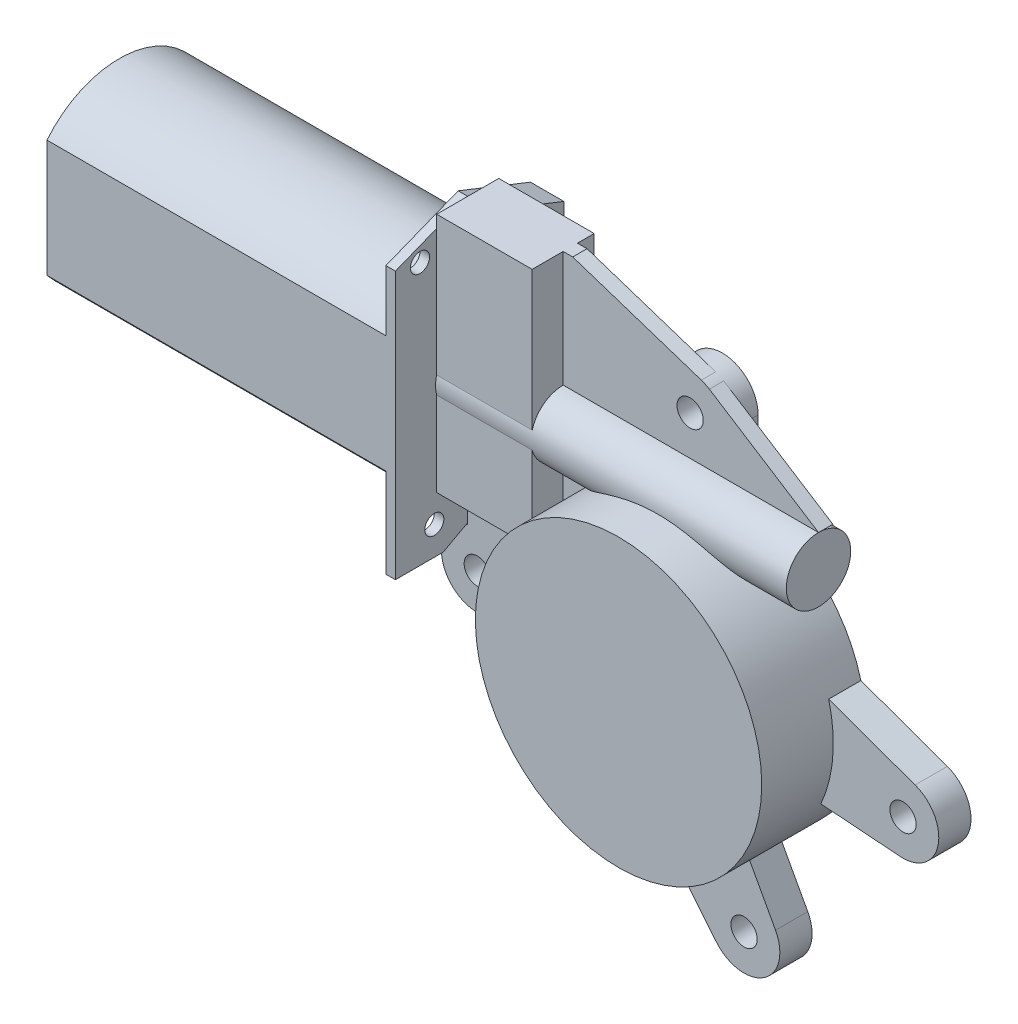
SolidWorks part; units mm, degrees
ref_plane "正面" through (0, 0, 0) normal (0, 0, 1) x (1, 0, 0)
ref_plane "平面" through (0, 0, 0) normal (0, 1, 0) x (1, 0, 0)
ref_plane "右側面" through (0, 0, 0) normal (1, 0, 0) x (0, 0, -1)
sketch "ｽｹｯﾁ2" plane through (0, 0, 0) normal (1, 0, 0) x (0, 0, -1)
  line L0 (0, 0) -> (0, 50000) construction
  line L1 (15.15, 12.2771) -> (15.15, -12.2771)
  line L2 (-15.15, 12.2771) -> (-15.15, -12.2771)
  arc A0 (-15.15, -12.2771) -> (15.15, -12.2771) centre (0, 0) ccw
  arc A2 (15.15, 12.2771) -> (-15.15, 12.2771) centre (0, 0) ccw
  dimension "D1" = 39
  dimension "D2" = 30.3
extrude "ﾎﾞｽ - 押し出し1" add sketch "ｽｹｯﾁ2" against normal blind 71
sketch "ｽｹｯﾁ3" plane through (-71, 0, 0) normal (-1, 0, 0) x (0, 0, 1)
  circle A0 centre (0, 0) radius 7
  dimension "D1" = 14
extrude "ﾎﾞｽ - 押し出し2" add sketch "ｽｹｯﾁ3" along normal blind 0.8
sketch "ｽｹｯﾁ4" plane through (-71.8, 0, 0) normal (-1, 0, 0) x (0, 0, 1)
  circle A0 centre (0, 0) radius 2.25
  dimension "D1" = 4.5
extrude "ﾎﾞｽ - 押し出し3" add sketch "ｽｹｯﾁ4" along normal blind 0.2
sketch "ｽｹｯﾁ5" plane through (0, 0, 0) normal (1, 0, 0) x (0, 0, -1)
  line L0 (0, 0) -> (0, 50000) construction
  line L1 (0, 0) -> (-50000, 0) construction
  line L2 (-15.15, 25) -> (-15.15, -20)
  line L3 (-15.15, -20) -> (5.15, -31)
  line L4 (5.15, -31) -> (15.15, -31)
  line L5 (15.15, -31) -> (15.15, 25)
  line L6 (15.15, 25) -> (0, 31)
  line L7 (0, 31) -> (-15.15, 25)
  line L8 (15.15, -12.2771) -> (15.15, 12.2771) construction
  line L9 (-15.15, 12.2771) -> (-15.15, -12.2771) construction
  circle A0 centre (0, 0) radius 26 construction
  circle A1 centre (0, 26) radius 2.5
  circle A2 centre (-10, 24) radius 2
  circle A3 centre (10, 24) radius 2
  circle A4 centre (7, -25.04) radius 2
  dimension "D6" = 52
  dimension "D8" = 5
  dimension "D9" = 4
  dimension "D10" = 7
  dimension "D11" = 4
  dimension "D2" = 31
  dimension "D3" = 25
  dimension "D4" = 62
  dimension "D5" = 20
  dimension "D7" = 10
  dimension "D12" = 10
extrude "ﾎﾞｽ - 押し出し4" add sketch "ｽｹｯﾁ5" along normal blind 2
sketch "ｽｹｯﾁ7" plane through (2, 0, 0) normal (1, 0, 0) x (0, 0, -1)
  circle A0 centre (0, 0) radius 6.75
  dimension "D1" = 13.5
extrude "ﾎﾞｽ - 押し出し7" add sketch "ｽｹｯﾁ7" along normal blind 73.5
sketch "ｽｹｯﾁ6" plane through (0, 0, 0) normal (0, 0, 1) x (1, 0, 0)
  line L0 (0, 0) -> (-50000, 0) construction
  line L1 (29.7505, -30) -> (-49970.2495, -30) construction
  line L2 (48.6, -30) -> (48.6, 49970) construction
  line L3 (2, 25) -> (2, -20) construction
  circle A0 centre (48.6, -30) radius 30
  dimension "D1" = 30
  dimension "D2" = 46.6
extrude "ﾎﾞｽ - 押し出し8" add sketch "ｽｹｯﾁ6" against normal blind 15
sketch "ｽｹｯﾁ8" plane through (0, 0, 0) normal (0, 0, 1) x (1, 0, 0)
  line L0 (48.6, -30) -> (48.6, 49970) construction
  line L1 (48.6, -30) -> (-49951.4, -30) construction
  line L2 (48.6, -36) -> (-49951.4, -36) construction
  line L3 (59.9, -30) -> (59.9, 49970) construction
  line L4 (54.1031, -78.2588) -> (37.3, -57.7905)
  line L5 (66.4901, -69.9194) -> (59.9, -57.7905)
  line L6 (92.6469, -43.4796) -> (75.9861, -42.2476)
  line L7 (95.741, -28.9436) -> (77.6268, -22.4207)
  line L8 (41.1, 15) -> (41.1, -0.9526)
  line L9 (56.1, 15) -> (56.1, -0.9526)
  line L10 (0.5475, -29.3419) -> (20.7407, -18.8709)
  line L11 (5.7319, -43.2973) -> (20.2627, -39.8487)
  arc A0 (41.1, -0.9526) -> (20.7407, -18.8709) centre (48.6, -30) ccw
  circle A1 centre (48.6, 15) radius 2.75
  circle A2 centre (4, -36) radius 2.75
  circle A3 centre (93.2, -36) radius 2.75
  circle A4 centre (59.9, -73.5) radius 2.75
  arc A5 (0.5475, -29.3419) -> (5.7319, -43.2973) centre (4, -36) ccw
  arc A6 (56.1, 15) -> (41.1, 15) centre (48.6, 15) ccw
  arc A7 (92.6469, -43.4796) -> (95.741, -28.9436) centre (93.2, -36) ccw
  arc A8 (54.1031, -78.2588) -> (66.4901, -69.9194) centre (59.9, -73.5) ccw
  arc A9 (29.6412, -6.75) -> (67.5588, -6.75) centre (48.6, -30) ccw construction
  arc A10 (59.9, -57.7905) -> (75.9861, -42.2476) centre (48.6, -30) ccw
  arc A11 (20.2627, -39.8487) -> (37.3, -57.7905) centre (48.6, -30) ccw
  arc A12 (77.6268, -22.4207) -> (56.1, -0.9526) centre (48.6, -30) ccw
  dimension "D3" = 60
  dimension "D4" = 43.5
  dimension "D5" = 44.6
  dimension "D6" = 44.6
  dimension "D8" = 5.5
  dimension "D9" = 15
  dimension "D1" = 11.3
  dimension "D2" = 6
  dimension "D7" = 45
extrude "ﾎﾞｽ - 押し出し9" add sketch "ｽｹｯﾁ8" along normal blind 6.75
sketch "ｽｹｯﾁ9" plane through (0, 0, 0) normal (0, 0, 1) x (1, 0, 0)
  line L0 (75.5, 6.75) -> (52.6308, 21.3247)
  line L1 (50.9466, 22.1235) -> (24, 31)
  line L2 (24, 31) -> (2, 31)
  line L3 (2, 31) -> (2, -28.5887)
  line L4 (20.7407, -18.8709) -> (0.5475, -29.3419) construction
  line L5 (2, -20) -> (2, -31) construction
  line L6 (2, -28.5887) -> (75.5, 6.75)
  arc A0 (56.1, 15) -> (41.1, 15) centre (48.6, 15) ccw construction
  arc A1 (50.9466, 22.1235) -> (52.6308, 21.3247) centre (48.6, 15) cw
  circle A2 centre (48.6, 15) radius 2.75
  dimension "D2" = 5.5
  dimension "D1" = 22
extrude "ﾎﾞｽ - 押し出し10" add sketch "ｽｹｯﾁ9" along normal blind 3 contours A1 L1 L2 L3 L6 L0 region at (28.0225, 5.7047, 0)
sketch "ｽｹｯﾁ10" plane through (0, 0, 0) normal (0, 0, 1) x (1, 0, 0)
  line L0 (2, 31) -> (22, 31)
  line L1 (24, 31) -> (2, 31) construction
  line L2 (22, 31) -> (22, -19.5)
  line L3 (22, -19.5) -> (2, -19.5)
  line L4 (2, 25) -> (2, -20) construction
  line L5 (2, -6.0467) -> (2, -26.5837) construction
  line L6 (-71, -19.5) -> (0, -19.5) construction
  line L7 (2, 31) -> (2, -19.5)
  dimension "D1" = 20
extrude "ﾎﾞｽ - 押し出し11" add sketch "ｽｹｯﾁ10" against normal blind 6.5 and the other way blind 6.5
sketch "ｽｹｯﾁ12" plane through (2, 0, 0) normal (1, 0, 0) x (0, 0, -1)
  line L0 (0, 0) -> (-50000, 0) construction
  line L1 (-15.15, 12) -> (-6.5, 19)
  line L2 (-15.15, 25) -> (-15.15, -20) construction
  line L4 (-6.5, 28.4257) -> (-6.5, 1.82) construction
  line L5 (-15.15, 12) -> (-15.15, -12)
  line L6 (-15.15, -12) -> (-6.5, -19)
  line L7 (-6.5, 19) -> (-6.5, -19)
  arc A0 (-6.5, 1.82) -> (-6.5, -1.82) centre (0, 0) ccw construction
  point P15 (-15.15, 0)
  point P16 (-6.75, 0)
  dimension "D1" = 24
  dimension "D2" = 38
extrude "ﾎﾞｽ - 押し出し19" add sketch "ｽｹｯﾁ12" along normal blind 18
sketch "ｽｹｯﾁ13" plane through (0, 0, 6.75) normal (0, 0, 1) x (1, 0, 0)
  circle A0 centre (48.6, -30) radius 10.5
  dimension "D1" = 21
extrude "ﾎﾞｽ - 押し出し20" add sketch "ｽｹｯﾁ13" along normal blind 7.5
sketch "ｽｹｯﾁ14" plane through (0, 0, 14.25) normal (0, 0, 1) x (1, 0, 0)
  circle A0 centre (48.6, -30) radius 5.85
  circle A1 centre (48.6, -30) radius 5.5
  dimension "D1" = 11
  dimension "D2" = 11.7
extrude "ｶｯﾄ - 押し出し1" cut sketch "ｽｹｯﾁ14" against normal blind 0.1
sketch "ｽｹｯﾁ15" plane through (0, 0, 15.15) normal (0, 0, 1) x (1, 0, 0)
  line L0 (0, 0) -> (-50000, 0) construction
  line L1 (2, 13.5772) -> (2, 50013.5772) construction
  line L3 (20, 8) -> (9, -19)
  line L4 (20, 1.82) -> (20, 19) construction
  line L5 (20, -19) -> (2, -19) construction
  line L6 (9, -19) -> (20, -19)
  line L7 (20, -19) -> (20, 8)
  dimension "D1" = 27
  dimension "D2" = 11
extrude "ｶｯﾄ - 押し出し2" cut sketch "ｽｹｯﾁ15" against normal blind 7.5
sketch "ｽｹｯﾁ16" plane through (2, 0, 0) normal (1, 0, 0) x (0, 0, -1)
  line L0 (-6.5, 28.4257) -> (-15.15, 25)
  line L1 (-15.15, 25) -> (-15.15, -20)
  line L2 (-15.15, -20) -> (-6.5, -24.6872)
  line L3 (-6.5, -24.6872) -> (-6.5, 28.4257)
  line L4 (-15.15, -20) -> (-3, -26.5837) construction
extrude "ﾎﾞｽ - 押し出し23" add sketch "ｽｹｯﾁ16" along normal blind 5
sketch "ｽｹｯﾁ17" plane through (0, 0, 6.75) normal (0, 0, 1) x (1, 0, 0)
  line L0 (48.6, -30) -> (48.6, -50030) construction
  line L1 (48.6, -30) -> (50048.6, -30) construction
  text T0 "→" font "MS UI Gothic" height in points 72
extrude "ｶｯﾄ - 押し出し3" cut sketch "ｽｹｯﾁ17" against normal blind 0.5
sketch "ｽｹｯﾁ18" plane through (0, 0, 14.25) normal (0, 0, 1) x (1, 0, 0)
  line L0 (48.6, -30) -> (50048.6, -30) construction
  line L1 (48.6, -30) -> (48.6, -50030) construction
  line L2 (42.9102, -16.2637) -> (19177.0818, -46210.2403) construction
  line L3 (110.94, -18.2904) -> (113.04, -18.2904) construction
  line L4 (110.94, -18.2904) -> (127.5765, -20.6285) construction
  line L5 (110.94, -18.2904) -> (110.873, -18.2904) construction
  line L6 (110.94, -18.2904) -> (110.8298, -18.3305) construction
  line L7 (46.8443, -21.7855) -> (45.4386, -22.3678) construction
  circle A0 centre (48.6, -30) radius 5.775 construction
  circle A1 centre (48.6, -30) radius 10.5 construction
  circle A2 centre (48.6, -30) radius 7.8934 construction
  circle A3 centre (48.6, -30) radius 8.4 construction
  arc A4 (44.628, -20.2803) -> (47.2686, -24.3806) centre (44.0049, -23.582) cw
  arc A5 (49.9314, -24.3806) -> (47.2686, -24.3806) centre (48.6, -30) ccw
  arc A6 (44.628, -20.2803) -> (52.572, -20.2803) centre (48.6, -30) cw
  arc A7 (52.572, -20.2803) -> (49.9314, -24.3806) centre (53.1951, -23.582) ccw
  circle M1 centre (48.6, -30) radius 5.85
  circle M2 centre (48.6, -30) radius 10.5
  dimension "D2" = 11.55
  dimension "D3" = 15.7868
  dimension "D4" = 21
  dimension "D5" = 16.8
  dimension "D6" = 3.36
  dimension "Ap" = 20
  dimension "Backlash" = 0.067
  dimension "m" = 2.1
  dimension "z" = 8
  dimension "d" = 16.8
  dimension "bl" = 0.1173
  dimension "D1" = 22.5
  dimension "D7" = 1.5215
extrude "ｶｯﾄ - 押し出し4" cut sketch "ｽｹｯﾁ18" against normal blind 7.5 contours A7 A4 M2 M1 region at (48.6, -21.4297, 14.25)
ref_plane "平面1" through (0, -30, 0) normal (0, 1, 0) x (-1, 0, 0)
sketch "ｽｹｯﾁ19" plane through (0, -30, 0) normal (0, 1, 0) x (-1, 0, 0)
  line L2 (-48.6, -7.5) -> (-48.6, 49992.5) construction
ref_axis "軸1" through (48.6, -30, -7.5) along (0, 0, 1)
pattern_circular "円形ﾊﾟﾀｰﾝ1" count 8 over 360 about axis through (48.6, -30, -7.5) along (0, 0, 1) of "ｶｯﾄ - 押し出し4"
ref_plane "平面2" through (0, 0, 15.15) normal (0, 0, 1) x (1, 0, 0)
mirror "ﾐﾗｰ1" about plane through (0, 0, 15.15) normal (0, 0, 1) of "円形ﾊﾟﾀｰﾝ1", "ｶｯﾄ - 押し出し4", "ｶｯﾄ - 押し出し3", "ﾎﾞｽ - 押し出し23", "ｶｯﾄ - 押し出し2", "ｶｯﾄ - 押し出し1", "ﾎﾞｽ - 押し出し20", "ﾎﾞｽ - 押し出し19", "ﾎﾞｽ - 押し出し11", "ﾎﾞｽ - 押し出し10", "ﾎﾞｽ - 押し出し9", "ﾎﾞｽ - 押し出し8", "ﾎﾞｽ - 押し出し7", "ﾎﾞｽ - 押し出し4", "ﾎﾞｽ - 押し出し3", "ﾎﾞｽ - 押し出し2", "ﾎﾞｽ - 押し出し1"
sketch "ｽｹｯﾁ20" plane through (0, 0, 15.15) normal (0, 0, 1) x (1, 0, 0)
  line L0 (-72, 2.25) -> (-72, -2.25) construction
  line L1 (100.7, 31) -> (-72, 31)
  line L2 (100.7, 31) -> (100.7, -81)
  line L3 (100.7, -81) -> (-72, -81)
  line L4 (-72, 31) -> (-72, -81)
  line L5 (22, 31) -> (2, 31) construction
  arc A0 (92.6469, -43.4796) -> (95.741, -28.9436) centre (93.2, -36) ccw construction
  arc A3 (54.1031, -78.2588) -> (66.4901, -69.9194) centre (59.9, -73.5) ccw construction
extrude "ｶｯﾄ - 押し出し5" cut sketch "ｽｹｯﾁ20" against normal through all
equation "\"bl@ｽｹｯﾁ18\" = \"Backlash@ｽｹｯﾁ18\"*7/4"
equation "\"d@ｽｹｯﾁ18\" = \"m@ｽｹｯﾁ18\"*\"z@ｽｹｯﾁ18\""
equation "\"D1@ｽｹｯﾁ18\" = 180/\"z@ｽｹｯﾁ18\""
equation "\"D2@ｽｹｯﾁ18\" = \"d@ｽｹｯﾁ18\"-2.5*\"m@ｽｹｯﾁ18\""
equation "\"D3@ｽｹｯﾁ18\" = \"d@ｽｹｯﾁ18\" *cos( \"Ap@ｽｹｯﾁ18\"* pi /180 ) "
equation "\"D4@ｽｹｯﾁ18\" = \"d@ｽｹｯﾁ18\"+2*\"m@ｽｹｯﾁ18\""
equation "\"D5@ｽｹｯﾁ18\" = \"d@ｽｹｯﾁ18\""
equation "\"D6@ｽｹｯﾁ18\" = \"d@ｽｹｯﾁ18\"/5"
equation "\"D7@ｽｹｯﾁ18\" = \"d@ｽｹｯﾁ18\"* sin(  pi /2/\"z@ｽｹｯﾁ18\" )/2 -\"bl@ｽｹｯﾁ18\""
